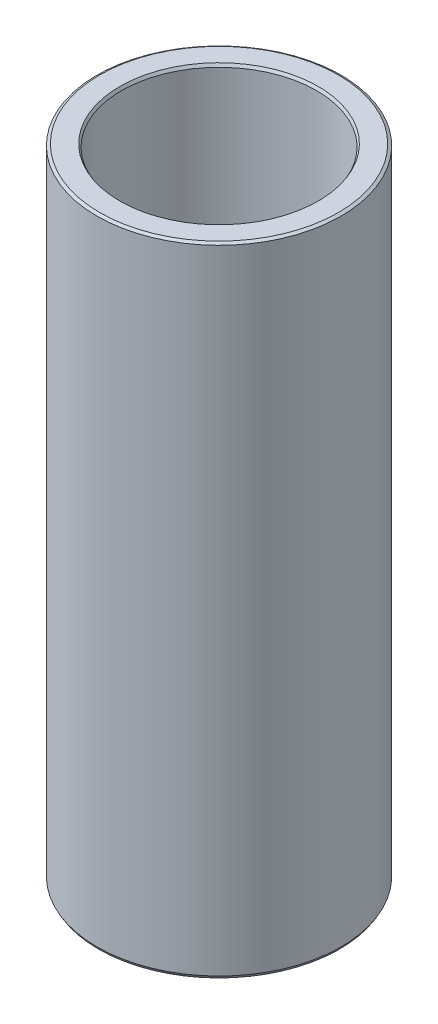
SolidWorks part; units mm, degrees
ref_plane "Front Plane" through (0, 0, 0) normal (0, 0, 1) x (1, 0, 0)
ref_plane "Top Plane" through (0, 0, 0) normal (0, 1, 0) x (1, 0, 0)
ref_plane "Right Plane" through (0, 0, 0) normal (1, 0, 0) x (0, 0, -1)
sketch "Sketch1" plane through (0, 0, 0) normal (0, 1, 0) x (1, 0, 0)
  circle A0 centre (0, 0) radius 50
  dimension "SLEEVE_OD" = 100
extrude "Boss-Extrude1" add sketch "Sketch1" along normal blind 260.9911
sketch "Sketch2" plane through (0, 0, 0) normal (0, 1, 0) x (1, 0, 0)
  circle A0 centre (0, 0) radius 39.9831
  dimension "BORE_D" = 79.9662
extrude "Cut-Extrude1" cut sketch "Sketch2" along normal through all
chamfer "Chamfer1" distance 0.6647 angle 60 4 edges at (0, 260.9911, 39.9831) (0, 0, 39.9831) (0, 0, 50) (0, 260.9911, 50) first distance on face at (0, 260.9911, 39.9831) first distance on face at (0, 0, 39.9831) first distance on face at (0, 260.9911, 50)
